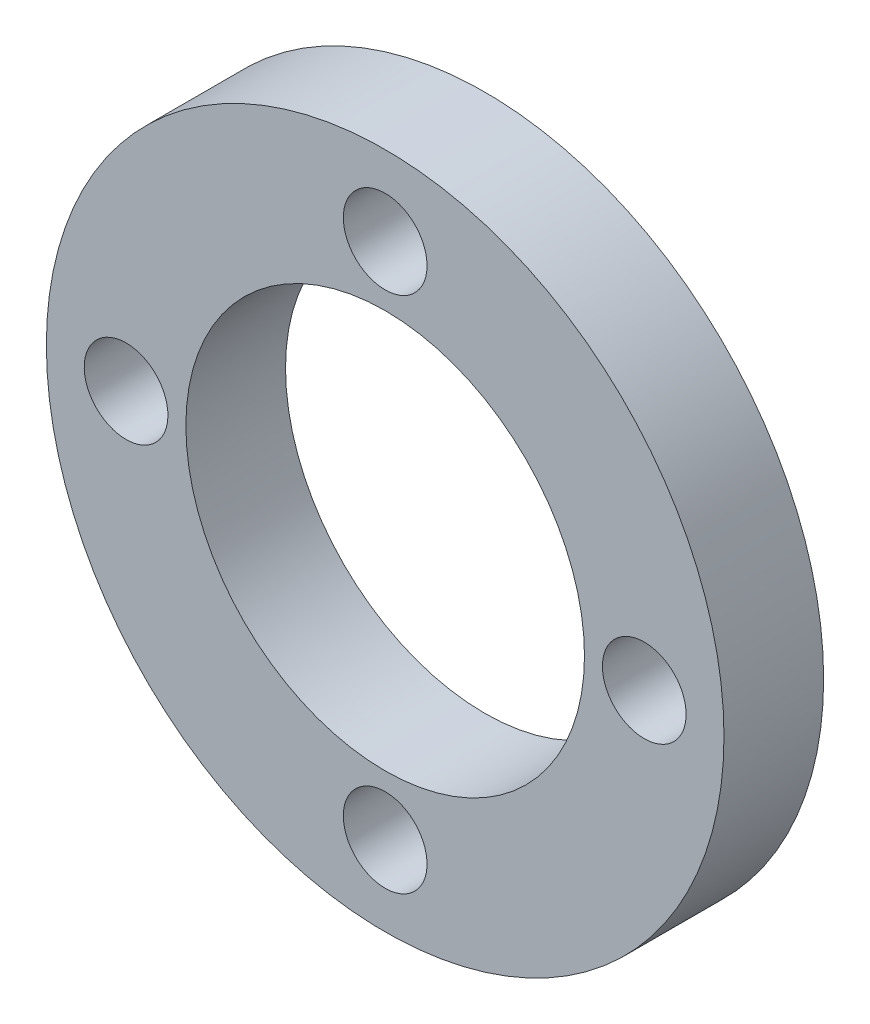
SolidWorks part; units mm, degrees
ref_plane "Plan de face" through (0, 0, 0) normal (0, 0, 1) x (1, 0, 0)
ref_plane "Plan de dessus" through (0, 0, 0) normal (0, 1, 0) x (1, 0, 0)
ref_plane "Plan de droite" through (0, 0, 0) normal (1, 0, 0) x (0, 0, -1)
sketch "Esquisse1" plane through (0, 0, 0) normal (0, 0, 1) x (1, 0, 0)
  circle A0 centre (0, 0) radius 17
  circle A1 centre (0, 0) radius 10
  dimension "D1" = 34
  dimension "D2" = 20
extrude "Extrusion1" add sketch "Esquisse1" along normal blind 5
sketch "Esquisse2" plane through (0, 0, 5) normal (0, 0, 1) x (1, 0, 0)
  line L0 (0, 0) -> (0, 13.8975) construction
  circle A0 centre (0, 13) radius 2.1
  dimension "D1" = 4.2
  dimension "D2" = 13
extrude "Enlèv. mat.-Extru.1" cut sketch "Esquisse2" against normal through all
ref_axis "Axe1" through (0, 0, 5) along (0, 0, -1)
pattern_circular "Répétition circulaire1" count 4 over 360 about axis through (0, 0, 5) along (0, 0, -1) of "Enlèv. mat.-Extru.1"
